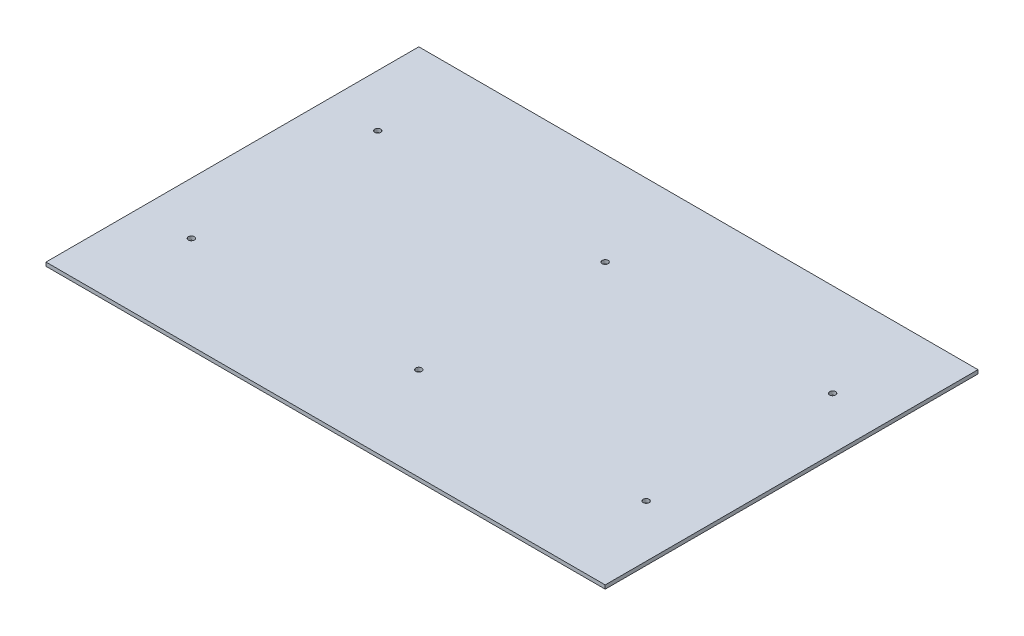
SolidWorks part; units mm, degrees
material "Stainless Steel (ferritic)"
ref_plane "Front Plane" through (0, 0, 0) normal (0, 0, 1) x (1, 0, 0)
ref_plane "Top Plane" through (0, 0, 0) normal (0, 1, 0) x (1, 0, 0)
ref_plane "Right Plane" through (0, 0, 0) normal (1, 0, 0) x (0, 0, -1)
sketch "Sketch1" plane through (0, 0, 0) normal (0, 1, 0) x (1, 0, 0)
  line L1 (-375, 250) -> (375, 250)
  line L2 (-375, 250) -> (-375, -250)
  line L3 (-375, -250) -> (375, -250)
  line L4 (375, 250) -> (375, -250)
  line L5 (-375, 250) -> (375, -250) construction
  line L6 (-375, -250) -> (375, 250) construction
  point P0 (0, 0)
extrude "Boss-Extrude1" add sketch "Sketch1" along normal blind 5
sketch "Sketch2" plane through (0, 5, 0) normal (0, 1, 0) x (1, 0, 0)
  line L0 (375, 250) -> (-375, 250) construction
  line L1 (375, -250) -> (375, 250) construction
  circle A0 centre (305, 125) radius 4
  dimension "D1" = 125
  dimension "D2" = 70
  dimension "D3" = 8
extrude "Cut-Extrude1" cut sketch "Sketch2" against normal blind 10
sketch "Sketch3" plane through (0, 5, 0) normal (0, 1, 0) x (1, 0, 0)
  line L0 (-375, -250) -> (375, -250) construction
  line L1 (375, -250) -> (375, 250) construction
  circle A0 centre (305, -125) radius 4
  dimension "D1" = 125
  dimension "D2" = 70
  dimension "D3" = 8
extrude "Cut-Extrude2" cut sketch "Sketch3" against normal blind 10
sketch "Sketch4" plane through (0, 5, 0) normal (0, 1, 0) x (1, 0, 0)
  line L0 (375, -250) -> (375, 250) construction
  line L1 (375, 250) -> (-375, 250) construction
  circle A0 centre (0, 125) radius 4
  dimension "D1" = 8
  dimension "D2" = 375
  dimension "D3" = 125
extrude "Cut-Extrude3" cut sketch "Sketch4" against normal blind 10
sketch "Sketch5" plane through (0, 5, 0) normal (0, 1, 0) x (1, 0, 0)
  circle A0 centre (0, -125) radius 4
extrude "Cut-Extrude4" cut sketch "Sketch5" against normal blind 10
sketch "Sketch6" plane through (0, 5, 0) normal (0, 1, 0) x (1, 0, 0)
  line L0 (-375, 250) -> (-375, -250) construction
  line L1 (375, 250) -> (-375, 250) construction
  circle A0 centre (-305, 125) radius 4
  dimension "D1" = 70
  dimension "D2" = 125
  dimension "D3" = 8
extrude "Cut-Extrude5" cut sketch "Sketch6" against normal blind 10
sketch "Sketch7" plane through (0, 5, 0) normal (0, 1, 0) x (1, 0, 0)
  line L0 (-375, 250) -> (-375, -250) construction
  line L1 (-375, -250) -> (375, -250) construction
  circle A0 centre (-305, -125) radius 4
  dimension "D1" = 8
  dimension "D2" = 70
  dimension "D3" = 125
extrude "Cut-Extrude6" cut sketch "Sketch7" against normal blind 10 contours A0
sketch "Sketch9" plane through (0, 5, 0) normal (0, 1, 0) x (1, 0, 0)
  line L0 (-375, 250) -> (0, 250) construction
  line L1 (375, 250) -> (-375, 250) construction
  line L2 (-187.5, 250) -> (-187.5, -250) construction
  line L3 (-375, -250) -> (375, -250) construction
